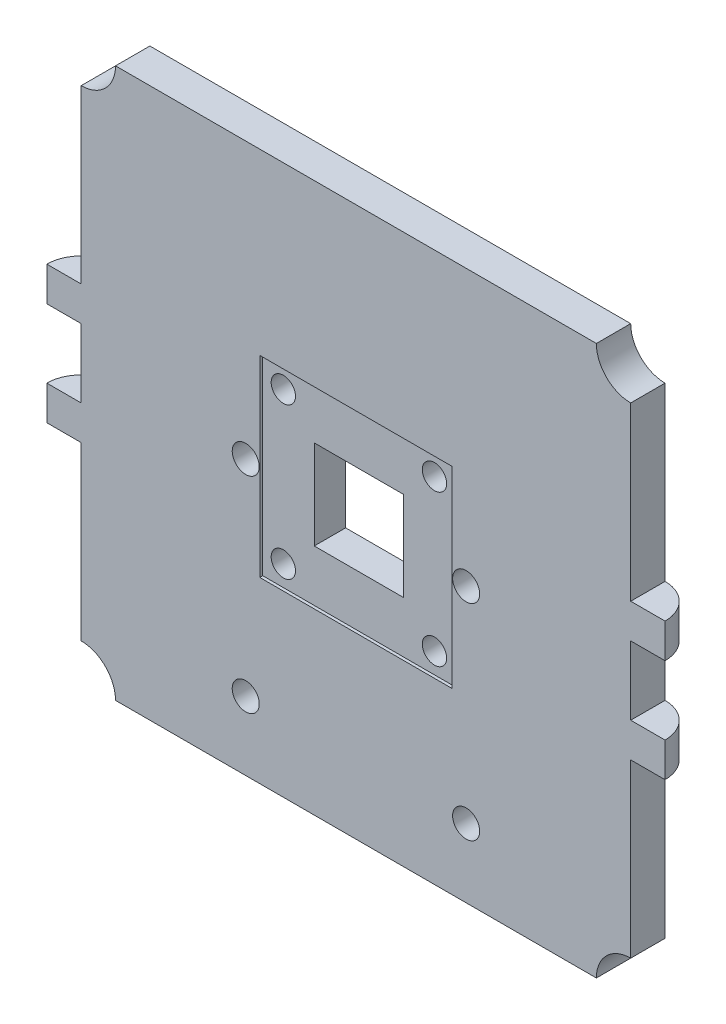
SolidWorks part; units mm, degrees
note: '?' marks a value the reader was unsure of. The reader was unsure of these and kept them because the rebuilt part matched: shared geometry of "Sketch5<3>", "Sketch13<4>", "Sketch13<5>", "Sketch13<6>".
ref_plane "Front Plane" through (0, 0, 0) normal (0, 0, 1) x (1, 0, 0)
ref_plane "Top Plane" through (0, 0, 0) normal (0, 1, 0) x (1, 0, 0)
ref_plane "Right Plane" through (0, 0, 0) normal (1, 0, 0) x (0, 0, -1)
sketch "Sketch1" plane through (0, 0, 0) normal (0, 1, 0) x (1, 0, 0)
  line L1 (-57.15, 57.15) -> (57.15, 57.15)
  line L2 (-57.15, 57.15) -> (-57.15, -57.15)
  line L3 (-57.15, -57.15) -> (57.15, -57.15)
  line L4 (57.15, 57.15) -> (57.15, -57.15)
  point P4 (0, 57.15)
  point P7 (-57.15, 0)
  dimension "D1" = 114.3
  dimension "D2" = 114.3
extrude "Boss-Extrude1" add sketch "Sketch1" along normal mid plane 107.95
sketch "Sketch2" plane through (0, 53.975, 0) normal (0, 1, 0) x (1, 0, 0)
  line L1 (-50.8, 50.8) -> (50.8, 50.8)
  line L2 (-50.8, 50.8) -> (-50.8, -50.8)
  line L3 (-50.8, -50.8) -> (50.8, -50.8)
  line L4 (50.8, 50.8) -> (50.8, -50.8)
  arc A0 (-50.8, 44.45) -> (-44.45, 50.8) centre (-50.8, 50.8) ccw
  arc A1 (44.45, 50.8) -> (50.8, 44.45) centre (50.8, 50.8) ccw
  arc A2 (-50.8, -44.45) -> (-44.45, -50.8) centre (-50.8, -50.8) cw
  arc A3 (44.45, -50.8) -> (50.8, -44.45) centre (50.8, -50.8) cw
  point P4 (0, 50.8)
  point P5 (50.8, 0)
  dimension "D3" = 6.35
  dimension "D4" = 6.35
  dimension "D5" = 6.35
  dimension "D6" = 6.35
  dimension "D1" = 101.6
  dimension "D2" = 101.6
extrude "Cut-Extrude1" cut sketch "Sketch2" against normal blind 101.6 contours L3 A3 L4 A1 L1 A0 L2 A2
sketch "Sketch5" plane through (0, 0, -50.8) normal (0, 0, 1) x (1, 0, 0)
  line L0 (8.255, 3.175) -> (-8.255, 3.175) construction
  line L1 (-17.78, 20.955) -> (17.78, 20.955)
  line L2 (-17.78, 20.955) -> (-17.78, -14.605)
  line L3 (-17.78, -14.605) -> (17.78, -14.605)
  line L4 (17.78, 20.955) -> (17.78, -14.605)
  line L5 (-8.255, 11.43) -> (8.255, 11.43)
  line L6 (-8.255, 11.43) -> (-8.255, -5.08)
  line L7 (-8.255, -5.08) -> (8.255, -5.08)
  line L8 (8.255, 11.43) -> (8.255, -5.08)
  line L9 (-57.15, -53.975) -> (57.15, -53.975) construction
  line L10 (-57.15, 53.975) -> (-57.15, -53.975) construction
  line L11 (0, 11.43) -> (0, -5.08) construction
  point P8 (0, 11.43)
  point P9 (0, 20.955)
  point P12 (17.78, 3.175)
  point P13 (8.255, 3.175)
  dimension "D1" = 35.56
  dimension "D2" = 16.51
  dimension "D3" = 16.51
  dimension "D4" = 35.56
  dimension "D5" = 39.37
  dimension "D6" = 39.37
extrude "Cut-Extrude5" cut sketch "Sketch5" against normal blind 0.55
extrude "Cut-Extrude6" cut sketch "Sketch5<3>" against normal up to next
sketch "Sketch5<3>" plane through (0, 0, -50.8) normal (0, 0, 1) x (1, 0, 0) same geometry as "Sketch5"
sketch "Sketch13" plane through (0, 0, -57.15) normal (0, 0, -1) x (-1, 0, 0)
  line L0 (-57.15, 53.975) -> (57.15, 53.975) construction
  line L1 (-57.15, 53.975) -> (-57.15, -53.975) construction
  line L2 (57.15, 53.975) -> (57.15, -53.975) construction
  line L3 (-14.2875, 27.94) -> (-14.2875, 22.86) construction
  line L4 (14.2875, 22.86) -> (14.2875, 27.94) construction
  line L5 (13.7875, 29.177) -> (13.7875, 21.623)
  line L6 (14.7875, 29.177) -> (14.7875, 21.623)
  line L7 (11.5934, 22.7059) -> (16.9816, 28.0941)
  line L8 (11.5934, 28.0941) -> (16.9816, 22.7059)
  circle A0 centre (-14.2875, 25.4) radius 2.54
  circle A1 centre (14.2875, 25.4) radius 2.54
  circle A2 centre (14.2875, 25.4) radius 3.81
  point P19 (13.7875, 25.4)
  point P20 (14.7875, 25.4)
  dimension "D1" = 5.08
  dimension "D2" = 5.08
  dimension "D7" = 7.62
  dimension "D3" = 28.575
  dimension "D4" = 28.575
  dimension "D5" = 42.8625
  dimension "D6" = 42.8625
  dimension "D8" = 1
  dimension "D9" = 0.5
  dimension "D10" = 45
  dimension "D11" = 45
extrude "Boss-Extrude2" add sketch "Sketch13" along normal blind 1.27 contours A0
ref_plane "Plane1" through (14.2875, 25.4, -57.15) normal (0, -1, 0) x (-1, 0, 0)
sketch "Sketch14" plane through (14.2875, 25.4, -57.15) normal (0, -1, 0) x (-1, 0, 0)
  line L0 (0, 1.27) -> (0, 2.54)
  line L1 (2.54, 1.27) -> (-2.54, 1.27) construction
  line L2 (0, 2.54) -> (2.286, 2.54)
  line L3 (2.286, 2.54) -> (2.64, 1.651)
  line L4 (2.64, 1.651) -> (2.64, 1.397)
  line L6 (2.54, 0) -> (2.54, 1.27) construction
  line L7 (2.54, 1.27) -> (0, 1.27)
  arc A0 (2.64, 1.397) -> (2.54, 1.27) centre (2.5094, 1.397) cw
  dimension "D2" = 0.1306
  dimension "D1" = 1.27
  dimension "D3" = 2.286
  dimension "D4" = 0.254
  dimension "D5" = 0.9569
revolve "Revolve1" add sketch "Sketch14" angle 360 about L0
ref_plane "Plane2" through (-14.2875, 25.4, -57.15) normal (0, -1, 0) x (-1, 0, 0)
extrude "Cut-Extrude7" cut sketch "Sketch13<4>" against normal blind 2.54 contours L8 A1 L7 L6 | L6 A1 L8 | L5 A1 L6 L8 L7 | L7 A1 L6 | L6 A1 L5 L8 L7 | L7 L8 L6 | L8 L5 L7 | L8 A1 L7 L5 | L7 A1 L5 | L5 A1 L8
sketch "Sketch13<4>" plane through (0, 0, -57.15) normal (0, 0, -1) x (-1, 0, 0) same geometry as "Sketch13"
extrude "Cut-Extrude8" cut sketch "Sketch13<5>" against normal blind 0.635 contours L7 A2 L5 A1 | L6 A2 L8 A1 | L7 A2 L6 A1 | L5 A2 L8 A1
sketch "Sketch13<5>" plane through (0, 0, -57.15) normal (0, 0, -1) x (-1, 0, 0) same geometry as "Sketch13"
extrude "Cut-Extrude9" cut sketch "Sketch13<6>" against normal blind 1.27 contours L6 A2 L5 A1 | L5 A2 L6 A1
sketch "Sketch13<6>" plane through (0, 0, -57.15) normal (0, 0, -1) x (-1, 0, 0) same geometry as "Sketch13"
sketch "Sketch17" plane through (-14.2875, 25.4, -57.15) normal (0, -1, 0) x (-1, 0, 0)
  line L0 (0, -1.27) -> (0, -2.54)
  line L1 (0.5, -1.27) -> (-0.5, -1.27) construction
  line L2 (0, -2.54) -> (2.286, -2.54)
  line L3 (2.286, -2.54) -> (2.64, -1.651)
  line L7 (2.54, -1.27) -> (0, -1.27)
  line L8 (2.64, -1.651) -> (2.64, -1.27)
  line L9 (2.64, -1.27) -> (2.54, -1.27)
  dimension "D1" = 2.54
  dimension "D2" = 2.286
  dimension "D3" = 0.1
  dimension "D4" = 1.27
  dimension "D5" = 0.381
revolve "Cut-Revolve1" cut sketch "Sketch17" angle 360 about L0
ref_plane "Plane3" through (0, 3.175, 0) normal (0, -1, 0) x (0, 0, 1)
ref_axis "Axis1" through (0, 3.175, 62.865) along (0, 0, -1)?
ref_axis "Axis2" through (0, 59.3725, 0) along (0, -1, 0)?
sketch "Sketch20" plane through (0, 0, -57.15) normal (0, 0, -1) x (-1, 0, 0)
  line L0 (-13.97, 3.175) -> (13.97, 3.175) construction
  line L1 (-13.97, 17.145) -> (13.97, 17.145)
  line L2 (-13.97, 17.145) -> (-13.97, -10.795)
  line L3 (-13.97, -10.795) -> (13.97, -10.795)
  line L4 (13.97, 17.145) -> (13.97, -10.795)
  point P4 (0, 17.145)
  point P9 (13.97, 3.175)
  dimension "D1" = 27.94
  dimension "D2" = 27.94
hole_wizard "CBORE for M5 Hex Head Bolt2" positions "3DSketch4" profile "Sketch21" counterbore size "M5" standard "ANSI Metric"
sketch3d "3DSketch4"
  point P0 (13.97, 17.145, -57.15)
  point P3 (-13.97, 17.145, -57.15)
  point P6 (-13.97, -10.795, -57.15)
  point P9 (13.97, -10.795, -57.15)
sketch "Sketch21" plane through (13.97, 17.145, -57.15) normal (1, 0, 0) x (0, 1, 0)
  line L0 (0, 0) -> (0, 18.288)
  line L1 (0, 18.288) -> (2.75, 16.6356)
  line L2 (2.75, 16.6356) -> (2.75, 5.8)
  line L3 (2.75, 5.8) -> (2.25, 5.8)
  line L4 (2.25, 5.8) -> (2.25, 0)
  line L5 (2.25, 0) -> (0, 0)
  line L10 (0, 18.288) -> (-2.75, 16.6356) construction
  line L11 (0, -6.35) -> (0, 107.95) construction
  dimension "Hole Dia." = 5.5
  dimension "Hole Depth" = 18.288
  dimension "C'Bore Dia." = 4.5
  dimension "C'Bore Depth" = 5.8
  dimension "Drill Angle" = 118
pattern_circular "CirPattern1" count 4 every 90 about axis through (0, 3.175, 0) along (0, 0, 1) of "Boss-Extrude2", "Revolve1", "Cut-Extrude7", "Cut-Extrude8", "Cut-Extrude9", "Cut-Revolve1"
sketch "Sketch26" plane through (0, 0, 57.15) normal (0, 0, 1) x (1, 0, 0)
  line L1 (-57.15, 53.975) -> (57.15, 53.975)
  line L2 (-57.15, 53.975) -> (-57.15, -53.975)
  line L3 (-57.15, -53.975) -> (57.15, -53.975)
  line L4 (57.15, 53.975) -> (57.15, -53.975)
extrude "Cut-Extrude11" cut sketch "Sketch26" against normal blind 107.95
sketch "Sketch27" plane through (0, 0, -57.15) normal (0, 0, -1) x (-1, 0, 0)
  line L0 (-20.375, -34.925) -> (-20.375, 3.075) construction
  line L1 (-20.375, 3.075) -> (20.375, 3.075) construction
  line L2 (20.375, 3.075) -> (20.375, -34.925) construction
  line L3 (20.375, -34.925) -> (-20.375, -34.925) construction
  line L4 (-57.15, -53.975) -> (57.15, -53.975) construction
  circle A0 centre (-20.375, 3.075) radius 2.5
  circle A1 centre (20.375, 3.075) radius 2.5
  circle A2 centre (20.375, -34.925) radius 2.5
  circle A3 centre (-20.375, -34.925) radius 2.5
  point P8 (0, 3.075)
  point P9 (0, -34.925)
  dimension "D4" = 5
  dimension "D5" = 5
  dimension "D6" = 5
  dimension "D7" = 5
  dimension "D1" = 38
  dimension "D2" = 40.75
  dimension "D3" = 19.05
extrude "Cut-Extrude12" cut sketch "Sketch27" against normal up to next
sketch "Sketch29" plane through (0, 0, -57.15) normal (0, 0, -1) x (-1, 0, 0)
  line L0 (-57.15, 53.975) -> (57.15, 53.975) construction
  line L1 (-50.8, 53.975) -> (50.8, 53.975)
  line L2 (-50.8, 53.975) -> (-50.8, -47.625)
  line L3 (-50.8, -47.625) -> (50.8, -47.625)
  line L4 (50.8, 53.975) -> (50.8, -47.625)
  line L5 (-57.15, 53.975) -> (-57.15, -53.975) construction
  line L7 (-57.15, -53.975) -> (57.15, -53.975) construction
  line L8 (-57.15, 15.875) -> (-50.8, 15.875)
  line L9 (-57.15, 53.975) -> (57.15, 53.975)
  line L10 (-57.15, 53.975) -> (-57.15, -53.975)
  line L11 (-57.15, -53.975) -> (57.15, -53.975)
  line L12 (57.15, 53.975) -> (57.15, -53.975)
  line L13 (-57.15, 15.875) -> (-57.15, 9.525)
  line L14 (-57.15, 9.525) -> (-50.8, 9.525)
  line L15 (-50.8, 15.875) -> (-50.8, 9.525)
  line L16 (-57.15, -3.175) -> (-50.8, -3.175)
  line L17 (-57.15, -3.175) -> (-57.15, -9.525)
  line L18 (-57.15, -9.525) -> (-50.8, -9.525)
  line L19 (-50.8, -3.175) -> (-50.8, -9.525)
  line L20 (50.8, 15.875) -> (57.15, 15.875)
  line L21 (50.8, 15.875) -> (50.8, 9.525)
  line L22 (50.8, 9.525) -> (57.15, 9.525)
  line L23 (57.15, 15.875) -> (57.15, 9.525)
  line L24 (50.8, -3.175) -> (57.15, -3.175)
  line L25 (50.8, -3.175) -> (50.8, -9.525)
  line L26 (50.8, -9.525) -> (57.15, -9.525)
  line L27 (57.15, -3.175) -> (57.15, -9.525)
  circle A0 centre (-50.8, 53.975) radius 6.35
  circle A1 centre (50.8, 53.975) radius 6.35
  circle A2 centre (50.8, -47.625) radius 6.35
  circle A3 centre (-50.8, -47.625) radius 6.35
  point P6 (0, 53.975)
  dimension "D3" = 12.7
  dimension "D4" = 12.7
  dimension "D5" = 12.7
  dimension "D6" = 12.7
  dimension "D1" = 6.35
  dimension "D2" = 6.35
  dimension "D7" = 6.35
  dimension "D8" = 6.35
  dimension "D9" = 6.35
  dimension "D10" = 6.35
  dimension "D11" = 38.1
  dimension "D12" = 38.1
  dimension "D13" = 38.1
  dimension "D14" = 38.1
extrude "Cut-Extrude13" cut sketch "Sketch29" against normal blind 6.35 contours A3 L2 A0 L10 | L9 A0 L2 | L2 A0 L1 | L2 A3 L3 | L3 A3 L2 | A3 L10 L11 | A2 L11 L12 | A3 L11 A2 L3 | A2 L4 L3 | L4 A2 L3 | A2 L12 A1 L4 | L4 A1 L9 | L1 A1 L4 | A3 L2 L18 L10 | A2 L12 L26 L4 | A1 L4 L20 L12 | A0 L10 L8 L2
fillet "Fillet1" radius 6.35 4 edges at (57.15, 12.7, -57.15) (57.15, -6.35, -57.15) (-57.15, -6.35, -57.15) (-57.15, 12.7, -57.15)
sketch "Sketch30" plane through (0, 0, -57.15) normal (0, 0, -1) x (-1, 0, 0)
  line L1 (-34.925, 38.1) -> (34.925, 38.1)
  line L2 (-34.925, 38.1) -> (-34.925, -31.75)
  line L3 (-34.925, -31.75) -> (34.925, -31.75)
  line L4 (34.925, 38.1) -> (34.925, -31.75)
  line L5 (-13.97, 3.175) -> (13.97, 3.175) construction
  circle A0 centre (-34.925, 38.1) radius 2.3812
  circle A1 centre (34.925, 38.1) radius 2.3812
  circle A2 centre (34.925, -31.75) radius 2.3812
  circle A3 centre (-34.925, -31.75) radius 2.3812
  point P4 (0, 38.1)
  point P6 (34.925, 3.175)
  point P9 (0, 3.175)
  dimension "D3" = 4.7625
  dimension "D4" = 4.7625
  dimension "D5" = 4.7625
  dimension "D6" = 4.7625
  dimension "D1" = 69.85
  dimension "D2" = 69.85
extrude "Cut-Extrude14" cut sketch "Sketch30" against normal blind 4.7625 contours A0 | A1 | A2 | A3
